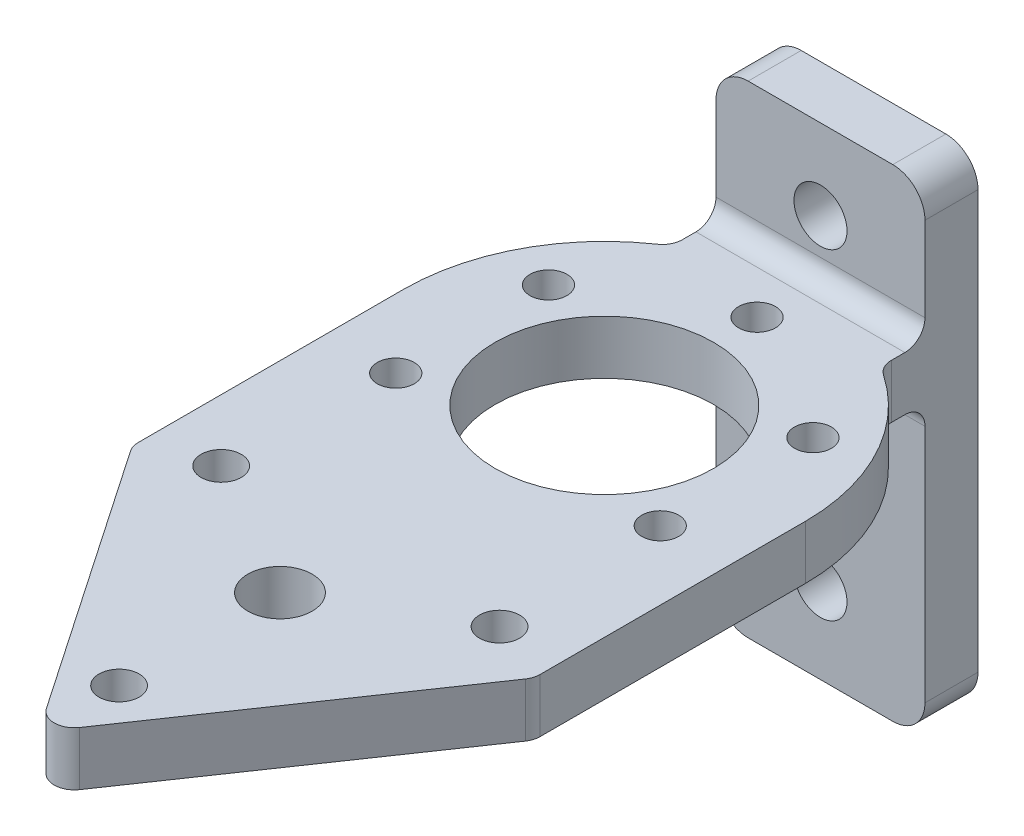
SolidWorks part; units mm, degrees
material "PLA"
ref_plane "Plan de face" through (0, 0, 0) normal (0, 0, 1) x (1, 0, 0)
ref_plane "Plan de dessus" through (0, 0, 0) normal (0, 1, 0) x (1, 0, 0)
ref_plane "Plan de droite" through (0, 0, 0) normal (1, 0, 0) x (0, 0, -1)
sketch "Esquisse1" plane through (0, 0, 0) normal (0, 0, 1) x (1, 0, 0)
  line L0 (55, 0) -> (-55, 0) construction
  line L1 (-6.5, -15) -> (6.5, -15)
  line L2 (-6.5, -15) -> (-6.5, 15)
  line L3 (-6.5, 15) -> (6.5, 15)
  line L4 (6.5, -15) -> (6.5, 15)
  line L5 (-6.5, -15) -> (6.5, 15) construction
  line L6 (-6.5, 15) -> (6.5, -15) construction
  circle A0 centre (0, 10) radius 1.65
  circle A1 centre (0, -10) radius 1.65
  point P0 (0, 0)
  dimension "D4" = 3.3
  dimension "D1" = 30
  dimension "D2" = 13
  dimension "D3" = 10
extrude "Boss.-Extru.1" add sketch "Esquisse1" along normal blind 3.3
fillet "Congé1" radius 2 4 edges at (6.5, -15, 1.65) (-6.5, -15, 1.65) (6.5, 15, 1.65) (-6.5, 15, 1.65)
sketch "Esquisse2" plane through (0, 0, 3.3) normal (0, 0, 1) x (1, 0, 0)
  line L0 (6.5, -13) -> (6.5, 13) construction
  line L3 (-6.5, 6.5) -> (6.5, 6.5)
  line L5 (-6.5, 13) -> (-6.5, -13) construction
  line L7 (-6.5, 6.5) -> (-6.5, 3.15)
  line L10 (-6.5, 3.15) -> (6.5, 3.15)
  line L14 (6.5, 6.5) -> (6.5, 3.15)
  point P0 (0, 0)
  point P8 (0, 0)
  dimension "D1" = 3.15
  dimension "D3" = 3.35
extrude "Boss.-Extru.2" add sketch "Esquisse2" along normal blind 2.77
sketch "Esquisse4" plane through (0, 6.5, 0) normal (0, 1, 0) x (1, 0, 0)
  line L1 (-6.5, -6.07) -> (6.5, -6.07)
  line L3 (-6.5, -27.4242) -> (6.5, -27.4242)
  circle A4 centre (0, -16.7471) radius 6.8
  arc A5 (-6.5, -6.07) -> (-6.5, -27.4242) centre (0, -16.7471) ccw
  arc A6 (6.5, -27.4242) -> (6.5, -6.07) centre (0, -16.7471) ccw
  point P25 (0, -16.7471)
  point P28 (0, -16.7471)
  dimension "D2" = 12.5
  dimension "D3" = 13
  dimension "D6" = 13.6
  dimension "D1" = 12.5
extrude "Boss.-Extru.4" add sketch "Esquisse4" against normal up to surface (3.35 mm away) up to face at (0, 3.15, 4.685)
sketch "Esquisse6" plane through (0, 6.5, 0) normal (0, 1, 0) x (1, 0, 0)
  line L2 (0, -16.7471) -> (8.2272, -11.9971) construction
  line L3 (0, -16.7471) -> (-8.2272, -11.9971) construction
  line L4 (0, -16.7471) -> (0, -7.2471) construction
  line L5 (0, -16.7471) -> (-8.2272, -21.4971) construction
  line L6 (0, -16.7471) -> (0, -26.2471) construction
  line L7 (0, -16.7471) -> (8.2272, -21.4971) construction
  circle A0 centre (0, -7.2471) radius 1.15
  circle A1 centre (-8.2272, -11.9971) radius 1.15
  circle A2 centre (8.2272, -11.9971) radius 1.15
  circle A3 centre (-8.2272, -21.4971) radius 1.15
  circle A7 centre (8.2272, -21.4971) radius 1.15
  dimension "D2" = 2.3
  dimension "D5" = 2.3
  dimension "D6" = 2.3
  dimension "D7" = 9.5
  dimension "D14" = 2.3
  dimension "D15" = 2.3
  dimension "D1" = 9.5
  dimension "D3" = 60
  dimension "D4" = 60
  dimension "D8" = 9.5
  dimension "D9" = 60
  dimension "D10" = 60
  dimension "D11" = 9.5
  dimension "D12" = 9.5
  dimension "D13" = 9.5
extrude "Enlèv. mat.-Extru.2" cut sketch "Esquisse6" against normal through all
sketch "Esquisse8" plane through (0, 6.5, 0) normal (0, 1, 0) x (1, 0, 0)
  line L6 (-6.5, -27.4242) -> (6.5, -27.4242) construction
  line L8 (0, -9.9471) -> (0, -23.5471) construction
  line L9 (0, -36.9271) -> (0, -27.4242) construction
  line L10 (0, -36.9271) -> (8.6603, -31.9271) construction
  line L11 (0, -36.9271) -> (-8.6603, -31.9271) construction
  line L16 (12.5, -16.7471) -> (12.5, -33.6271) construction
  line L17 (-12.5, -16.7471) -> (-12.5, -33.6258) construction
  line L18 (0, -51.9371) -> (-12.5, -33.6258)
  line L19 (-12.5, -33.6258) -> (-12.5, -16.7471)
  line L20 (0, -51.9371) -> (12.5, -33.6271)
  line L21 (12.5, -33.6271) -> (12.5, -16.7471)
  line L22 (-6.5, -27.4242) -> (6.5, -27.4242)
  circle A0 centre (0, -36.9271) radius 2
  circle A1 centre (0, -36.9271) radius 10 construction
  circle A2 centre (8.6603, -31.9271) radius 1.25
  circle A3 centre (0, -16.7471) radius 6.8 construction
  circle A4 centre (-8.6603, -31.9271) radius 1.25
  circle A7 centre (0, -46.9371) radius 1.25
  arc A8 (6.5, -27.4242) -> (6.5, -6.07) centre (0, -16.7471) ccw construction
  arc A9 (-6.5, -6.07) -> (-6.5, -27.4242) centre (0, -16.7471) ccw construction
  arc A11 (-12.5, -16.7471) -> (-6.5, -27.4242) centre (0, -16.7471) ccw
  arc A12 (12.5, -16.7471) -> (6.5, -27.4242) centre (0, -16.7471) cw
  point P16 (0, -16.7471)
  point P32 (0, 0)
  point P33 (0, 0)
  dimension "D2" = 4
  dimension "D5" = 2.5
  dimension "D6" = 2.5
  dimension "D7" = 2.5
  dimension "D12" = 10.01
  dimension "D1" = 20.18
  dimension "D3" = 120
  dimension "D4" = 60
  dimension "D8" = 16.8787
  dimension "D9" = 16.88
  dimension "D10" = 5
  dimension "D11" = 8.6603
extrude "Boss.-Extru.5" add sketch "Esquisse8" against normal up to surface (3.35 mm away) up to face at (0, 3.15, 8.3971)
fillet "Congé2" radius 1.25 7 edges at (12.5, 4.825, 33.6271) (-12.5, 4.825, 33.6258) (0, 4.825, 51.9371) (0, 3.15, 3.3) (0, 6.5, 3.3) (6.5, 4.825, 6.07) (-6.5, 4.825, 6.07)
